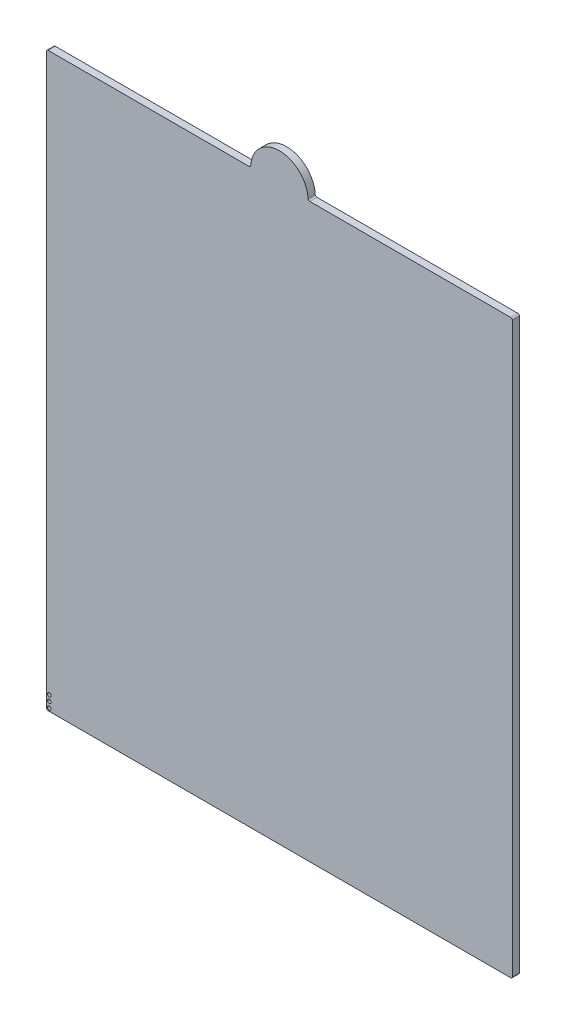
SolidWorks part; units mm, degrees
material "Acrylic (Medium-high impact)"
ref_plane "Front Plane" through (0, 0, 0) normal (0, 0, 1) x (1, 0, 0)
ref_plane "Top Plane" through (0, 0, 0) normal (0, 1, 0) x (1, 0, 0)
ref_plane "Right Plane" through (0, 0, 0) normal (1, 0, 0) x (0, 0, -1)
sketch "Sketch1" plane through (0, 0, 0) normal (0, 0, 1) x (1, 0, 0)
  line L1 (0, 0) -> (206.253, 0)
  line L2 (0, 0) -> (0, 253.103)
  line L3 (0, 253.103) -> (206.253, 253.103)
  line L4 (206.253, 0) -> (206.253, 253.103)
  dimension "D1" = 253.103
  dimension "D2" = 206.253
extrude "Boss-Extrude1" add sketch "Sketch1" along normal blind 3.175
sketch "Sketch4" [suppressed] plane through (0, 0, 3.175) normal (0, 0, 1) x (1, 0, 0)
  line L0 (0, 0) -> (206.253, 0) construction
  line L1 (-25.4, -25.4) -> (1193.8, -25.4)
  line L2 (-25.4, -25.4) -> (-25.4, 1193.8)
  line L3 (-25.4, 1193.8) -> (1193.8, 1193.8)
  line L4 (1193.8, -25.4) -> (1193.8, 1193.8)
  line L5 (0, 253.103) -> (0, 0) construction
  dimension "D1" = 25.4
  dimension "D2" = 25.4
  dimension "D3" = 1219.2
sketch "Sketch3" plane through (0, 0, 0) normal (0, 0, 1) x (1, 0, 0)
  line L0 (206.253, 253.103) -> (0, 253.103) construction
  line L1 (90.4265, 253.103) -> (115.8265, 253.103)
  line L2 (103.1265, 0) -> (103.1265, 265.803) construction
  line L3 (0, 0) -> (206.253, 0) construction
  arc A0 (115.8265, 253.103) -> (90.4265, 253.103) centre (103.1265, 253.103) ccw
  point P9 (103.1265, 265.803)
  dimension "D1" = 25.4
extrude "Boss-Extrude3" add sketch "Sketch3" along normal blind 3.175
fillet "Fillet1" radius 0.7937 6 edges at (0, 0, 1.5875) (206.253, 0, 1.5875) (206.253, 253.103, 1.5875) (0, 253.103, 1.5875) (90.4265, 253.103, 1.5875) (115.8265, 253.103, 1.5875)
sketch "Sketch5" plane through (0, 0, 3.175) normal (0, 0, 1) x (1, 0, 0)
  line L0 (0, 252.3092) -> (0, 0.7937) construction
  line L1 (0.7937, 0) -> (205.4592, 0) construction
  circle A0 centre (1.27, 1.27) radius 0.7938
  dimension "D2" = 1.5875
  dimension "D1" = 1.27
  dimension "D3" = 1.27
extrude "Cut-Extrude1" cut sketch "Sketch5" against normal blind 2.54
pattern_linear "LPattern1" count 3 spacing 2.54 along (0, 1, 0) of "Cut-Extrude1"
